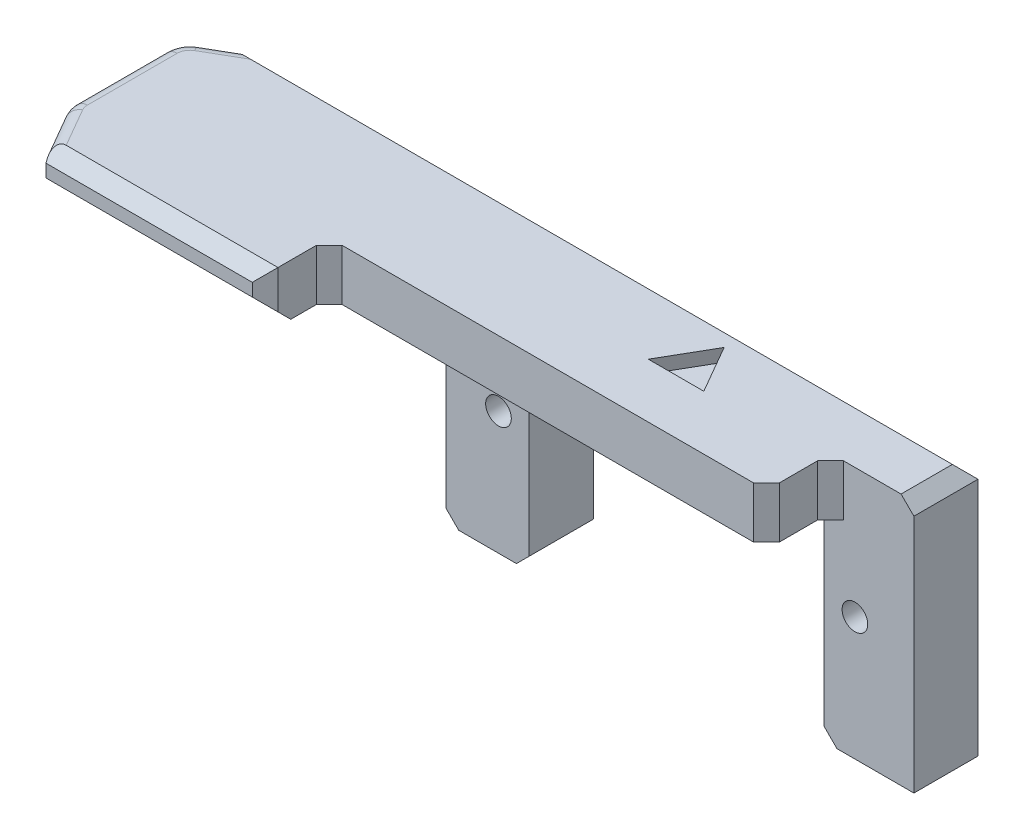
SolidWorks part; units mm, degrees
ref_plane "Front Plane" through (0, 0, 0) normal (0, 0, 1) x (1, 0, 0)
ref_plane "Top Plane" through (0, 0, 0) normal (0, 1, 0) x (1, 0, 0)
ref_plane "Right Plane" through (0, 0, 0) normal (1, 0, 0) x (0, 0, -1)
sketch "Sketch1" plane through (0, 0, 0) normal (0, 0, 1) x (1, 0, 0)
  line L1 (-19.3526, 63.35) -> (17.1474, 63.35)
  line L2 (-19.3526, 63.35) -> (-19.3526, 44.15)
  line L3 (-19.3526, 44.15) -> (17.1474, 44.15)
  line L4 (17.1474, 63.35) -> (17.1474, 44.15)
  dimension "D1" = 36.5
  dimension "D2" = 19.2
extrude "Boss-Extrude1" add sketch "Sketch1" along normal blind 5
sketch "Sketch2" plane through (0, 0, 5) normal (0, 0, 1) x (1, 0, 0)
  line L0 (17.1474, 63.35) -> (-19.3526, 63.35) construction
  line L1 (-12.8526, 59.85) -> (10.1474, 59.85)
  line L2 (-12.8526, 59.85) -> (-12.8526, 44.15)
  line L3 (-12.8526, 44.15) -> (10.1474, 44.15)
  line L4 (10.1474, 59.85) -> (10.1474, 44.15)
  line L5 (17.1474, 44.15) -> (17.1474, 63.35) construction
  line L6 (-19.3526, 44.15) -> (17.1474, 44.15) construction
  circle A0 centre (-15.2526, 53.75) radius 1
  circle A1 centre (12.5474, 53.75) radius 1
  dimension "D5" = 2
  dimension "D8" = 2
  dimension "D1" = 23
  dimension "D3" = 3.5
  dimension "D4" = 7
  dimension "D6" = 6.1
  dimension "D7" = 2.4
  dimension "D9" = 2.4
  dimension "D10" = 6.1
extrude "Cut-Extrude3" cut sketch "Sketch2" against normal through all
sketch "Sketch4" plane through (0, 63.35, 0) normal (0, 1, 0) x (1, 0, 0)
  line L1 (17.1474, 0) -> (-42.8526, 0)
  line L2 (17.1474, 0) -> (17.1474, -15)
  line L3 (17.1474, -15) -> (-42.8526, -15)
  line L4 (-42.8526, 0) -> (-42.8526, -15)
  dimension "D1" = 60
  dimension "D2" = 15
extrude "Boss-Extrude2" add sketch "Sketch4" along normal blind 0.5
sketch "Sketch7" plane through (0, 63.35, 0) normal (0, -1, 0) x (1, 0, 0)
  line L1 (-19.3526, 0) -> (-42.8526, 0)
  line L2 (-19.3526, 0) -> (-19.3526, 5)
  line L3 (-19.0526, 15) -> (-42.8526, 15)
  line L4 (-42.8526, 0) -> (-42.8526, 15)
  line L5 (17.1474, 15) -> (-19.0526, 15)
  line L6 (17.1474, 15) -> (17.1474, 5)
  line L7 (17.1474, 5) -> (-19.3526, 5)
extrude "Boss-Extrude3" add sketch "Sketch7" along normal blind 3.5 contours L1 L4 L3 L5 L6 L7 L2
chamfer "Chamfer1" distance 2 angle 45 1 edges at (-12.8526, 59.85, 15)
chamfer "Chamfer2" distance 1 angle 45 7 edges at (-19.3526, 59.85, 2.5) (-19.3526, 44.15, 2.5) (-12.8526, 63.85, 15) (17.1474, 63.85, 7.5) (-12.8526, 63.85, 0) (10.1474, 44.15, 2.5) (-12.8526, 44.15, 2.5)
chamfer "Chamfer3" distance 4 angle 30 2 edges at (-42.8526, 61.35, 0) (-42.8526, 62.35, 15)
fillet "Fillet1" radius 2 2 edges at (-42.8526, 61.85, 11) (-42.8526, 61.85, 2.3094)
sketch "Sketch8" plane through (0, 63.85, 0) normal (0, 1, 0) x (1, 0, 0)
  line L0 (16.1474, -14) -> (16.1474, -1) construction
  line L1 (-0.6526, -2) -> (-2.8177, -5.75)
  line L2 (-2.8177, -5.75) -> (1.5124, -5.75)
  line L3 (1.5124, -5.75) -> (-0.6526, -2)
  line L4 (16.1474, -1) -> (-40.5847, -1) construction
  circle A0 centre (-0.6526, -4.5) radius 1.25 construction
  dimension "D1" = 2.5
  dimension "D2" = 16.8
  dimension "D3" = 3.5
  dimension "D4" = 3.75
extrude "Cut-Extrude4" cut sketch "Sketch8" against normal blind 1
fillet "Fillet2" radius 1 10 edges at (-41.2187, 63.85, 1.366) (-42.5847, 63.85, 2.4641) (-41.8526, 63.85, 12.7321) (-42.7845, 63.85, 10.9817) (-40.3526, 59.85, 0.866) (-42.5847, 59.85, 2.4641) (-42.1413, 59.85, 12.2321) (-42.7845, 59.85, 10.9817) (-42.8526, 63.85, 6.9641) (-42.8526, 59.85, 6.9641)
sketch "Sketch9" plane through (0, 63.85, 0) normal (0, 1, 0) x (1, 0, 0)
  line L1 (17.1474, -5) -> (10.6474, -5)
  line L2 (17.1474, -5) -> (17.1474, -15)
  line L3 (17.1474, -15) -> (9.6474, -15)
  line L4 (10.6474, -5) -> (10.6474, -10)
  line L6 (-42.8526, -10.4641) -> (-42.8526, -3.4641) construction
  line L7 (-23.4526, -15) -> (9.6474, -15)
  line L8 (-23.4526, -15) -> (-23.4526, -10)
  line L9 (-23.4526, -10) -> (10.6474, -10)
  line L11 (17.1474, -15) -> (-40.5432, -15) construction
  line L12 (17.1474, 0) -> (17.1474, -15) construction
  dimension "D1" = 6.5
  dimension "D2" = 19.4
  dimension "D3" = 5
  dimension "D4" = 10
extrude "Cut-Extrude5" cut sketch "Sketch9" against normal blind 10
chamfer "Chamfer4" distance 1 angle 45 4 edges at (10.6474, 61.85, 5) (-23.4526, 61.85, 10) (10.6474, 61.85, 10) (-23.4526, 62.35, 15)
